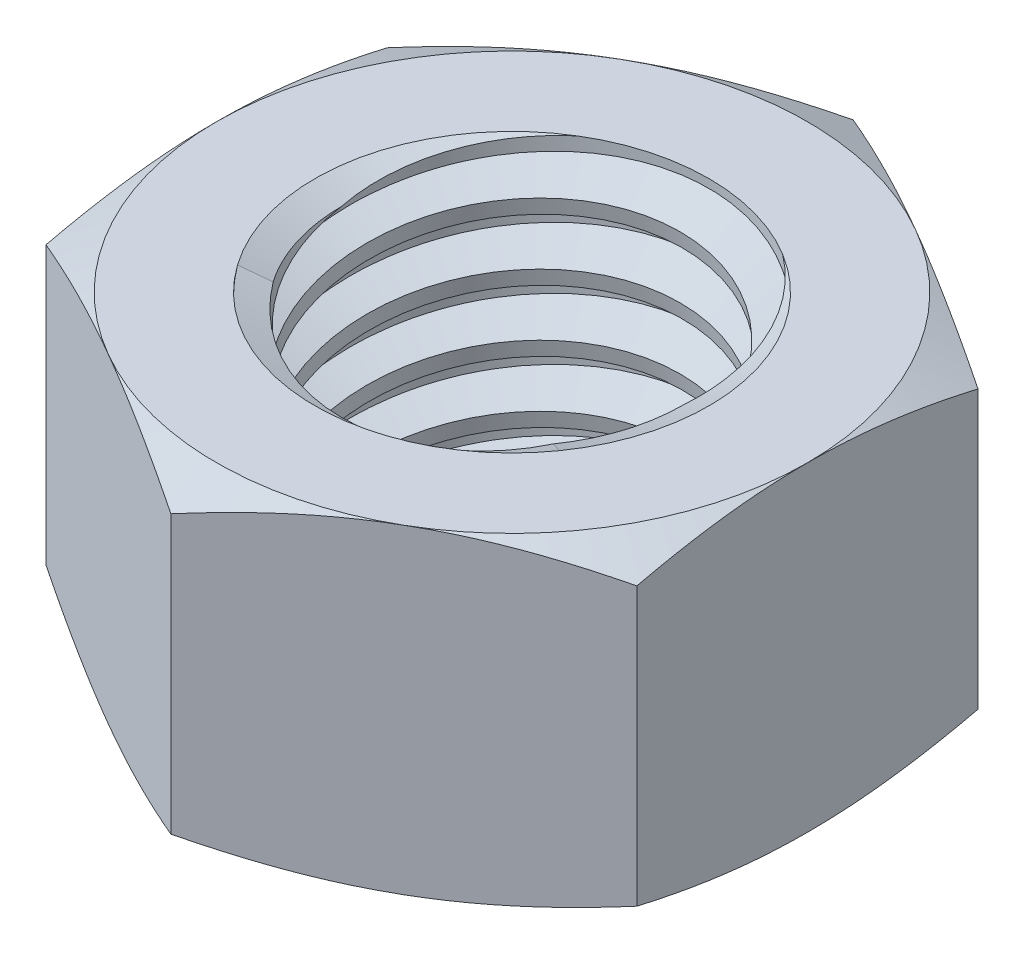
SolidWorks part; units mm, degrees
ref_plane "Front" through (0, 0, 0) normal (0, 0, 1) x (1, 0, 0)
ref_plane "Top" through (0, 0, 0) normal (0, 1, 0) x (1, 0, 0)
ref_plane "Right" through (0, 0, 0) normal (1, 0, 0) x (0, 0, -1)
sketch "Sketch1" plane through (0, 0, 0) normal (0, 1, 0) x (1, 0, 0)
  line L1 (0, 6.9282) -> (-6, 3.4641)
  line L2 (-6, 3.4641) -> (-6, -3.4641)
  line L3 (-6, -3.4641) -> (0, -6.9282)
  line L4 (0, -6.9282) -> (6, -3.4641)
  line L5 (6, -3.4641) -> (6, 3.4641)
  line L6 (6, 3.4641) -> (0, 6.9282)
  circle A0 centre (0, 0) radius 6 construction
  dimension "Hex Flats" = 12
extrude "Extrude1" add sketch "Sketch1" along normal mid plane 6.5
sketch "Sketch2" plane through (0, 0, 0) normal (1, 0, 0) x (0, 0, -1)
  line L0 (-4, -3.25) -> (-4, 3.25) construction
  line L1 (0, -3.25) -> (4, -3.25)
  line L2 (0, -3.25) -> (0, 3.25)
  line L3 (0, 3.25) -> (4, 3.25)
  line L4 (4, -3.25) -> (4, 3.25)
  line L5 (-3.4641, 3.25) -> (3.4641, 3.25) construction
  line L6 (-3.4641, -3.25) -> (3.4641, -3.25) construction
  line L7 (0, -7.25) -> (0, -3.25) construction
  dimension "Thread Dia" = 8
revolve "Revolve1" add sketch "Sketch2" angle 360 about L7
sketch "Sketch3" plane through (0, 0, 0) normal (1, 0, 0) x (0, 0, -1)
  line L0 (4, 3.25) -> (-4, 3.25) construction
  line L1 (-4, 3.25) -> (-4, 2) construction
  line L2 (-4, 2) -> (4, 3.25) construction
  line L3 (4, 3.25) -> (4.0241, 3.0956) construction
  line L4 (4.0241, 3.0956) -> (4.193, 2.015)
  line L5 (4.193, 2.015) -> (3.4642, 2.2965)
  line L6 (3.4642, 2.2965) -> (3.416, 2.6052)
  line L7 (3.416, 2.6052) -> (4.0241, 3.0956)
  line L8 (3.4401, 2.4509) -> (4.1085, 2.5553) construction
  line L9 (4, 3.25) -> (4, 2.5383) construction
  line L10 (4, 2.5383) -> (-4, 1.2883) construction
  line L11 (-4, 1.2883) -> (-4, 2) construction
  line L12 (-0.2089, 3.25) -> (0.2089, 0.5767) construction
  line L13 (-4, -3.25) -> (-4, 3.25) construction
  line L14 (0, 3.25) -> (4, 3.25) construction
  line L15 (4, -3.25) -> (4, 3.25) construction
  line L16 (0, 0) -> (0, 3.25) construction
  line L17 (-4.0241, 3.0956) -> (-4.193, 2.015) construction
  line L18 (-3.416, 2.6052) -> (-4.0241, 3.0956) construction
  line L19 (-3.4642, 2.2965) -> (-3.416, 2.6052) construction
  line L20 (-4.193, 2.015) -> (-3.4642, 2.2965) construction
  line L21 (0.2089, 3.25) -> (-0.2089, 0.5767) construction
  point P13 (0, 1.9133)
  dimension "D1" = 0.1562
  dimension "D2" = 0.3125
  dimension "Thread Pitch" = 1.25
  dimension "D4" = 60
  dimension "D5" = 1.25
revolve "Cut-Revolve1" cut sketch "Sketch3" angle 360 about L12
pattern_linear "LPattern1" count 5 spacing 1.25 along (0, -1, 0) count 2 spacing 1.25 along (0, 1, 0) of "Cut-Revolve1"
sketch "Sketch4" plane through (0, 0, 0) normal (1, 0, 0) x (0, 0, -1)
  line L0 (0, 3.25) -> (4, 3.25)
  line L1 (4, 3.25) -> (3.416, 2.9777)
  line L2 (3.416, 2.9777) -> (3.416, -2.9777)
  line L3 (3.416, -2.9777) -> (4, -3.25)
  line L4 (4, -3.25) -> (0, -3.25)
  line L5 (0, -3.25) -> (0, 3.25)
  line L6 (4, -3.25) -> (4, 3.25) construction
  line L7 (0, 3.25) -> (4, 3.25) construction
  line L8 (0, -3.25) -> (4, -3.25) construction
  line L9 (0, -3.25) -> (0, 3.25) construction
  line L10 (0, 3.25) -> (0, 3.8944) construction
  dimension "D1" = 25
revolve "Cut-Revolve2" cut sketch "Sketch4" angle 360 about L10
combine bodies "Combine1" operation type subtract main body 112 bodies to subtract 111
sketch "Sketch5" plane through (0, 0, 0) normal (1, 0, 0) x (0, 0, -1)
  line L0 (0, -3.25) -> (6, -3.25)
  line L1 (6, -3.25) -> (6.9282, -2.8172)
  line L2 (6.9282, -2.8172) -> (6.9282, 2.8172)
  line L3 (6.9282, 2.8172) -> (6, 3.25)
  line L4 (0, 3.25) -> (0, 4.52)
  line L5 (0, 4.52) -> (8.1982, 4.52)
  line L6 (8.1982, 4.52) -> (8.1982, -4.52)
  line L7 (8.1982, -4.52) -> (0, -4.52)
  line L8 (0, -4.52) -> (0, -3.25)
  line L9 (6, 3.25) -> (6, -3.25) construction
  line L11 (0, -3.25) -> (4, -3.25) construction
  line L12 (6, 3.25) -> (0, 3.25)
  line L13 (6.9282, 0) -> (8.1982, 0) construction
  line L14 (6.9282, 3.25) -> (6.9282, -3.25) construction
  line L15 (0, -3.25) -> (0, 3.25) construction
  line L17 (0, 0) -> (6, 0) construction
  line L22 (0, 3.25) -> (4, 3.25) construction
  dimension "D1" = 25
  dimension "D2" = 1.27
  dimension "D3" = 6.5
revolve "Cut-Revolve3" cut sketch "Sketch5" angle 360 about L15
equation "\"D1@Sketch3\"=\"Thread Pitch@Sketch3\"/8"
equation "\"D2@Sketch3\"=\"Thread Pitch@Sketch3\"/4"
equation "\"D5@Sketch3\"=\"Thread Pitch@Sketch3\""
equation "\"D4@LPattern1\"=\"Thread Pitch@Sketch3\""
equation "\"D3@LPattern1\"=\"Thread Pitch@Sketch3\""
equation "\"D1@LPattern1\"=\"Height@Extrude1\"/\"Thread Pitch@Sketch3\""
